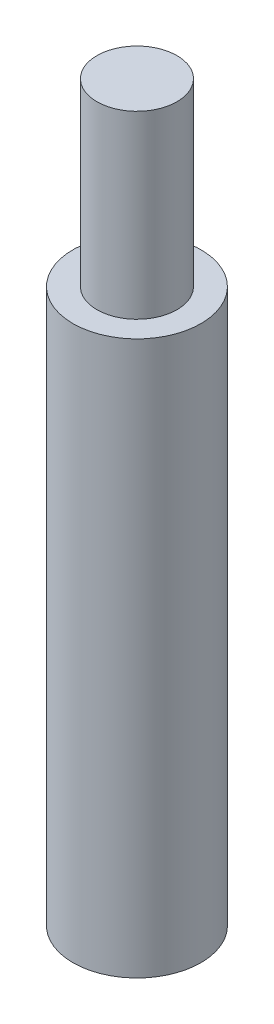
SolidWorks part; units mm, degrees
ref_plane "Front Plane" through (0, 0, 0) normal (0, 0, 1) x (1, 0, 0)
ref_plane "Top Plane" through (0, 0, 0) normal (0, 1, 0) x (1, 0, 0)
ref_plane "Right Plane" through (0, 0, 0) normal (1, 0, 0) x (0, 0, -1)
sketch "Sketch1" plane through (0, 0, 0) normal (0, 1, 0) x (1, 0, 0)
  circle A0 centre (0, 0) radius 5.08
  dimension "D1" = 10.16
extrude "Boss-Extrude1" add sketch "Sketch1" along normal blind 58.24
sketch "Sketch2" plane through (0, 58.24, 0) normal (0, 1, 0) x (1, 0, 0)
  circle A0 centre (0, 0) radius 3.175
  circle A2 centre (0, 0) radius 5.08
  circle A3 centre (0, 0) radius 5.08
  dimension "D2" = 6.35
  dimension "D1" = 0
extrude "Cut-Extrude1" cut sketch "Sketch2" against normal blind 14.3
